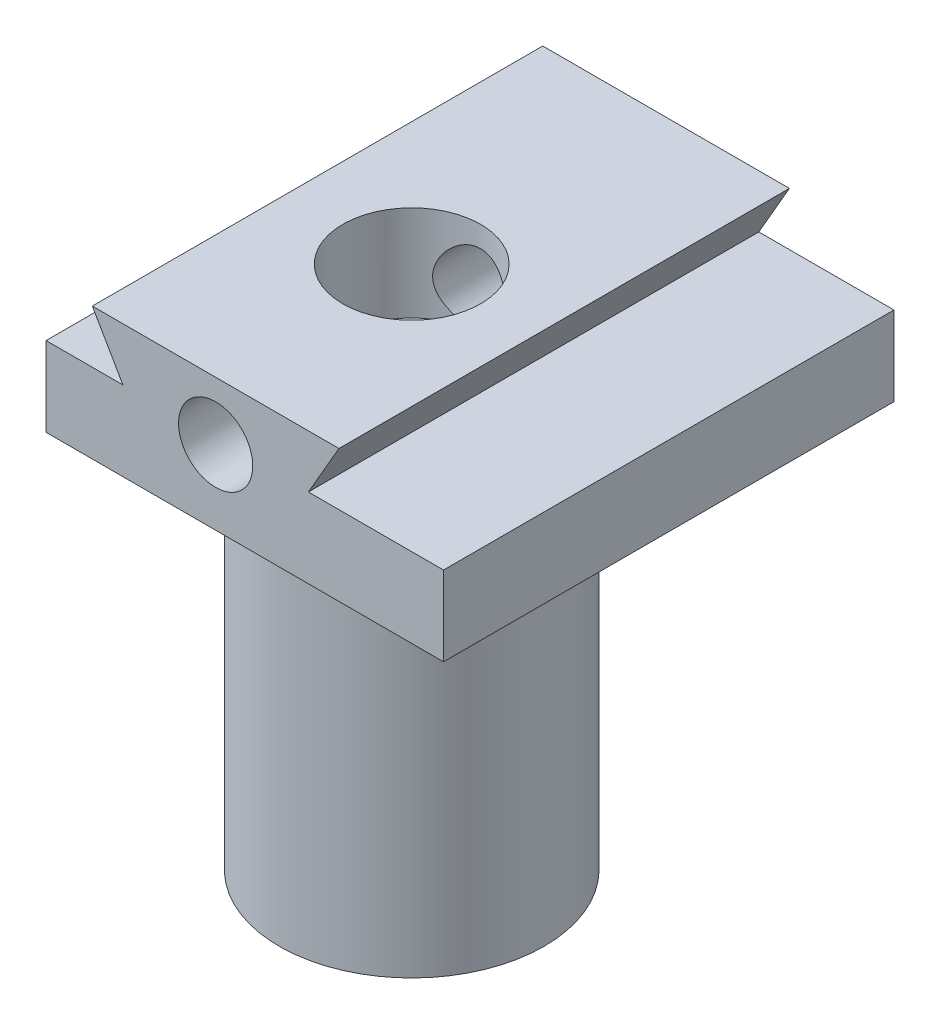
SolidWorks part; units mm, degrees
ref_plane "Front Plane" through (0, 0, 0) normal (0, 0, 1) x (1, 0, 0)
ref_plane "Top Plane" through (0, 0, 0) normal (0, 1, 0) x (1, 0, 0)
ref_plane "Right Plane" through (0, 0, 0) normal (1, 0, 0) x (0, 0, -1)
sketch "Sketch1" plane through (0, 0, 0) normal (0, 0, 1) x (1, 0, 0)
  line L0 (-130.6044, 21.0854) -> (-130.6044, 36.0854)
  line L1 (-130.6044, 36.0854) -> (-116.1044, 36.0854)
  line L2 (-116.1044, 36.0854) -> (-121.8779, 46.0854)
  line L3 (-121.8779, 46.0854) -> (-75.3309, 46.0854)
  line L4 (-75.3309, 46.0854) -> (-81.1044, 36.0854)
  line L5 (-81.1044, 36.0854) -> (-55.6044, 36.0854)
  line L6 (-55.6044, 36.0854) -> (-55.6044, 21.0854)
  line L7 (-55.6044, 21.0854) -> (-71.5797, 21.0854)
  line L12 (-130.6044, 21.0854) -> (-115.5797, 21.0854)
  line L16 (-156.9633, 18.0854) -> (-30.6816, 18.0854) construction
  line L17 (-98.6044, 69.0242) -> (-98.6044, -76.9901) construction
  line L18 (-201.9729, 36.0854) -> (37.647, 36.0854) construction
  line L24 (-115.5797, 21.0854) -> (-71.5797, 21.0854)
  line L25 (-98.6044, 28.0854) -> (-88.2044, 28.0854) construction
  circle A1 centre (-98.6044, 35.0854) radius 7
  dimension "D10" = 25
  dimension "D11" = 75
  dimension "D15" = 14
  dimension "D16" = 14
  dimension "D1" = 60
  dimension "D2" = 15
  dimension "D3" = 60
  dimension "D4" = 35
  dimension "D5" = 15
  dimension "D13" = 32
  dimension "D14" = 17.5
extrude "Boss-Extrude1" add sketch "Sketch1" along normal blind 85
sketch "Sketch4" plane through (0, 46.0854, 0) normal (0, 1, 0) x (1, 0, 0)
  line L0 (-130.6044, -85) -> (-130.6044, 0) construction
  line L1 (-75.3309, 0) -> (-121.8779, 0) construction
  circle A0 centre (-98.6044, -48) radius 13
  circle A1 centre (-98.6044, -48) radius 10
  dimension "D3" = 26
  dimension "D4" = 20
  dimension "D1" = 32
  dimension "D2" = 48
extrude "Cut-Extrude1" cut sketch "Sketch4" against normal blind 85 contours A1
extrude "Cut-Extrude2" cut sketch "Sketch4<4>" against normal blind 18
sketch "Sketch4<4>" plane through (0, 46.0854, 0) normal (0, 1, 0) x (1, 0, 0) same geometry as "Sketch4"
sketch "Sketch5" plane through (0, 21.0854, 0) normal (0, -1, 0) x (1, 0, 0)
  line L0 (-98.6044, 58) -> (-98.6044, 26.9226) construction
  line L1 (-88.6044, 48) -> (-114.2358, 48) construction
  circle A0 centre (-98.6044, 48) radius 10 construction
  circle A1 centre (-98.6044, 48) radius 25
  circle A3 centre (-98.6044, 48) radius 22
  circle M3 centre (-98.6044, 48) radius 10
  dimension "D1" = 50
  dimension "D2" = 44
extrude "Boss-Extrude4" add sketch "Sketch5" along normal blind 74 separate body contours A3 M3 | A1 A3 region at (-122.8973, 21.0854, 48) region at (-119.9821, 21.0854, 48)
extrude "Cut-Extrude6" cut sketch "Sketch5<6>" along normal blind 3 contours A1 A3 region at (-122.8973, 21.0854, 48)
sketch "Sketch5<6>" plane through (0, 21.0854, 0) normal (0, -1, 0) x (1, 0, 0) same geometry as "Sketch5"
sketch "Sketch7" plane through (0, -52.9146, 0) normal (0, -1, 0) x (1, 0, 0)
  line L0 (-123.6044, 48) -> (-40.9524, 48) construction
  line L1 (-98.6044, 73) -> (-98.6044, 12.6852) construction
  circle A0 centre (-98.6044, 48) radius 25 construction
  circle A1 centre (-98.6044, 48) radius 22
  dimension "D1" = 44
extrude "Cut-Extrude7" cut sketch "Sketch7" against normal blind 7
ref_plane "Plane1" through (-123.6044, 0, 0) normal (-1, 0, 0) x (0, 0, 1)
sketch "Sketch8" plane through (-123.6044, 0, 0) normal (-1, 0, 0) x (0, 0, 1)
  line L0 (48, -52.9146) -> (48, 23.9812) construction
  line L1 (23, -52.9146) -> (73, -52.9146) construction
  line L2 (55, -32.9146) -> (55, 9.0854)
  line L3 (41, 9.0854) -> (41, -32.9146)
  line L4 (41, -32.9146) -> (36.4612, -32.9146) construction
  circle A0 centre (48, -24.9146) radius 3
  circle A1 centre (48, 1.0854) radius 3
  arc A2 (41, 9.0854) -> (55, 9.0854) centre (48, 9.0854) cw
  arc A3 (55, -32.9146) -> (41, -32.9146) centre (48, -32.9146) cw
  dimension "D1" = 6
  dimension "D2" = 6
  dimension "D4" = 28
  dimension "D3" = 26
  dimension "D5" = 20
  dimension "D6" = 42
extrude "Cut-Extrude9" cut sketch "Sketch8" against normal blind 17 contours A1 | A0 region at (-123.6044, -24.9146, 48) region at (-123.6044, 1.0854, 48)
extrude "Cut-Extrude10" cut sketch "Sketch8<4>" against normal blind 6 contours A3 L2 A2 L3 A1 A0 region at (-123.6044, -11.9146, 48)
sketch "Sketch8<4>" plane through (-123.6044, 0, 0) normal (-1, 0, 0) x (0, 0, 1) same geometry as "Sketch8"
sketch "Sketch9" plane through (0, -45.9146, 0) normal (0, -1, 0) x (1, 0, 0)
  line L0 (-108.6044, 48) -> (-82.1053, 48) construction
  line L1 (-89.412, 38.8076) -> (-98.6044, 48) construction
  line L2 (-98.6044, 35.3178) -> (-98.6044, 66.5156) construction
  line L3 (-107.7967, 38.8076) -> (-98.6044, 48) construction
  line L4 (-98.6044, 48) -> (-89.412, 57.1924) construction
  line L5 (-98.6044, 48) -> (-107.7967, 57.1924) construction
  line L6 (-98.6044, 48) -> (-107.7967, 57.1924) construction
  circle A0 centre (-98.6044, 48) radius 10 construction
  circle A3 centre (-107.7967, 57.1924) radius 2.5
  circle A4 centre (-89.412, 57.1924) radius 2.5
  circle A5 centre (-89.412, 38.8076) radius 2.5
  circle A6 centre (-107.7967, 38.8076) radius 2.5
  dimension "D1" = 45
  dimension "D2" = 45
  dimension "D3" = 45
  dimension "D4" = 45
  dimension "D5" = 45
extrude "Cut-Extrude12" cut sketch "Sketch9" against normal blind 20
